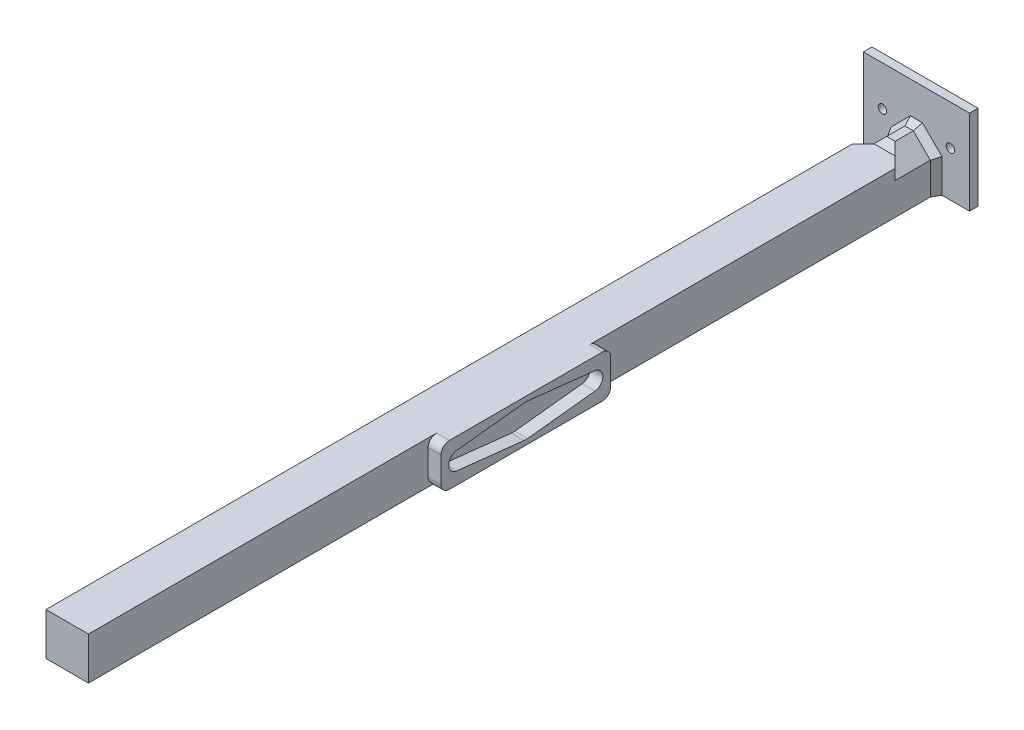
SolidWorks part; units mm, degrees
ref_plane "Ebene vorne" through (0, 0, 0) normal (0, 0, 1) x (1, 0, 0)
ref_plane "Ebene oben" through (0, 0, 0) normal (0, 1, 0) x (1, 0, 0)
ref_plane "Ebene rechts" through (0, 0, 0) normal (1, 0, 0) x (0, 0, -1)
sketch "Sketch1" plane through (0, 0, 0) normal (0, 0, 1) x (1, 0, 0)
  line L1 (5, -5) -> (-5, -5)
  line L2 (5, -5) -> (5, 5)
  line L3 (5, 5) -> (-5, 5)
  line L4 (-5, -5) -> (-5, 5)
  line L5 (5, -5) -> (-5, 5) construction
  line L6 (5, 5) -> (-5, -5) construction
  point P0 (0, 0)
  dimension "D1" = 10
  dimension "D2" = 10
extrude "Boss-Extrude1" add sketch "Sketch1" along normal mid plane 200
sketch "Sketch2" plane through (0, 0, -100) normal (0, 0, -1) x (-1, 0, 0)
  line L0 (-12.5, -5) -> (12.5, -5)
  line L1 (12.5, -5) -> (12.5, 15)
  line L2 (12.5, 15) -> (-12.5, 15)
  line L3 (-12.5, 15) -> (-12.5, -5)
  line L4 (0, 27.0368) -> (0, -6.5283) construction
  circle A0 centre (-8, 5.6) radius 1
  circle A1 centre (8, 5.6) radius 1
  dimension "D6" = 2
  dimension "D1" = 25
  dimension "D2" = 12.5
  dimension "D3" = 20
  dimension "D4" = 9.4
  dimension "D5" = 8
extrude "Boss-Extrude2" add sketch "Sketch2" along normal blind 2 contours L3 L0 L1 L2 | A0 | A1
sketch "Sketch4" plane through (0, 5, 0) normal (0, 1, 0) x (1, 0, 0)
  line L0 (-5, 100) -> (-5, 92.5)
  line L1 (-5, -100) -> (-5, 100) construction
  line L3 (-2.5, 92.5) -> (-2.5, 100)
  line L4 (-12.5, 100) -> (12.5, 100) construction
  line L5 (-2.5, 100) -> (-5, 100)
  line L6 (0, 100.9562) -> (0, 89.5783) construction
  line L7 (2.5, 92.5) -> (2.5, 100)
  line L9 (5, 100) -> (5, 92.5)
  line L10 (2.5, 100) -> (5, 100)
  line L11 (-2.5, 92.5) -> (-5, 90)
  line L12 (-5, 90) -> (-5, 92.5)
  line L13 (2.5, 92.5) -> (5, 90)
  line L14 (2.5, 92.5) -> (2.5, 100)
  line L15 (2.5, 100) -> (5, 100)
  line L16 (5, 100) -> (5, 92.5)
  line L17 (5, 90) -> (5, 92.5)
  line L18 (5, 92.5) -> (5, 90)
  line M6 (5, 100) -> (-5, 100)
  line M9 (5, -100) -> (5, 100)
  dimension "D1" = 2.5
  dimension "D2" = 7.5
  dimension "D3" = 135
extrude "Cut-Extrude2" cut sketch "Sketch4" against normal blind 2.5 contours L7 L13 M9 M6 | L12 L0 L5 L3 L11 region at (3.8095, 5, -95.5952)
chamfer "Chamfer2" distance 2.5 angle 45 2 edges at (-2.5, 2.5, -96.25) (2.5, 2.5, -96.25)
sketch "Sketch5" plane through (0, 0, -100) normal (0, 0, 1) x (1, 0, 0)
  line L0 (-2.5, 5) -> (-1, 6.5)
  line L1 (1, 6.5) -> (2.5, 5)
  line L2 (-1, 6.5) -> (1, 6.5)
  line L3 (-2.5, 5) -> (2.5, 5)
  dimension "D1" = 2
extrude "Boss-Extrude3" add sketch "Sketch5" along normal blind 7.5
sketch "Sketch7" plane through (5, 0, 0) normal (1, 0, 0) x (0, 0, -1)
  line L0 (92.5, 5) -> (94, 6.5)
  line L1 (92.5, 6.5) -> (100, 6.5) construction
  line L2 (94, 6.5) -> (92.5, 6.5)
  line L3 (92.5, 6.5) -> (92.5, 5)
extrude "Cut-Extrude3" cut sketch "Sketch7" against normal blind 7.5
chamfer "Chamfer3" distance 1 angle 60 5 edges at (5, -1.25, -100) (3, 4.5, -100) (0, 6.5, -100) (-3, 4.5, -100) (-5, -1.25, -100) first distance on face at (7, 5.6, -100)
sketch "Sketch8" plane through (5, 0, 0) normal (1, 0, 0) x (0, 0, -1)
  line L0 (0, 16.9193) -> (0, -19.8211) construction
  line L1 (-19.8908, 0) -> (20.7243, 0) construction
  line L2 (16.2681, 1.9881) -> (0.4089, 3.7276)
  line L3 (16.2681, -1.9881) -> (0.4089, -3.7276)
  line L4 (-16.2681, -1.9881) -> (-0.4089, -3.7276)
  line L5 (-16.2681, 1.9881) -> (-0.4089, 3.7276)
  line L6 (16.279, 2.0875) -> (0.4198, 3.827)
  line L7 (-16.279, 2.0875) -> (-0.4198, 3.827)
  line L8 (-16.279, -2.0875) -> (-0.4198, -3.827)
  line L9 (16.279, -2.0875) -> (0.4198, -3.827)
  line L10 (20, 5) -> (20, -5)
  line L11 (-100, 5) -> (90, 5) construction
  line L12 (-100, -5) -> (98.2679, -5) construction
  line L13 (20, -5) -> (-20, -5)
  line L14 (20, 5) -> (-20, 5)
  line L15 (-20, 5) -> (-20, -5)
  line L16 (102, 15) -> (102, -5) construction
  line L17 (-100, -5) -> (-100, 5) construction
  arc A0 (0.4089, 3.7276) -> (-0.4089, 3.7276) centre (0, 0) ccw
  arc A1 (16.2681, -1.9881) -> (16.2681, 1.9881) centre (16.05, 0) ccw
  arc A2 (-16.2681, -1.9881) -> (-16.2681, 1.9881) centre (-16.05, 0) cw
  arc A3 (-0.4089, -3.7276) -> (0.4089, -3.7276) centre (0, 0) ccw
  arc A4 (0.4198, 3.827) -> (-0.4198, 3.827) centre (0, 0) ccw
  arc A5 (-16.279, -2.0875) -> (-16.279, 2.0875) centre (-16.05, 0) cw
  arc A6 (-0.4198, -3.827) -> (0.4198, -3.827) centre (0, 0) ccw
  arc A7 (16.279, -2.0875) -> (16.279, 2.0875) centre (16.05, 0) ccw
  point P37 (0, -5)
  point P38 (0, 5)
  line M11 (-100, -5) -> (98.2679, -5)
  line M15 (90, 5) -> (-100, 5)
  dimension "D1" = 7.5
  dimension "D2" = 4
  dimension "D3" = 16.05
  dimension "D5" = 20
  dimension "D4" = 0.1
extrude "Boss-Extrude4" add sketch "Sketch8" along normal blind 3 contours L15 L10 A7 L9 A6 L8 A5 L7 A4 L6 M15 M11 region at (5, 0, -19.5877)
fillet "Fillet1" radius 2 4 edges at (6.5, 5, 20) (6.5, -5, 20) (6.5, -5, -20) (6.5, 5, -20)
sketch "Sketch9" plane through (-5, 0, 0) normal (-1, 0, 0) x (0, 0, 1)
  circle A0 centre (0, 0) radius 3
  dimension "D1" = 6
extrude "Cut-Extrude4" cut sketch "Sketch9" against normal blind 5
